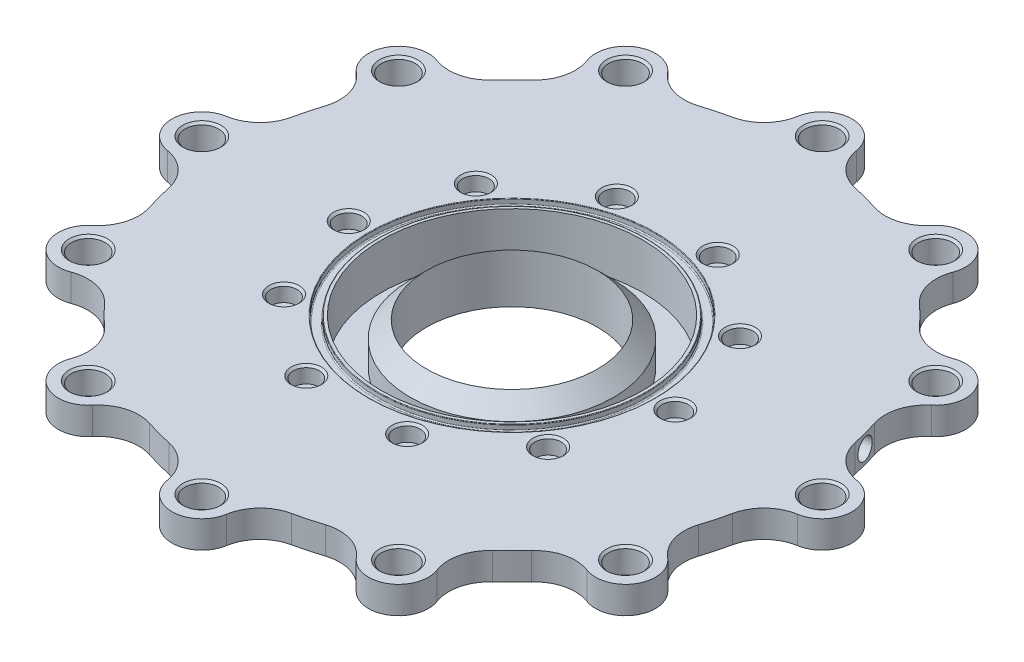
SolidWorks part; units mm, degrees
material "Inconel 718"
ref_plane "Front Plane" through (0, 0, 0) normal (0, 0, 1) x (1, 0, 0)
ref_plane "Top Plane" through (0, 0, 0) normal (0, 1, 0) x (1, 0, 0)
ref_plane "Right Plane" through (0, 0, 0) normal (1, 0, 0) x (0, 0, -1)
sketch "Sketch1" plane through (0, 0, 0) normal (0, 0, 1) x (1, 0, 0)
  line L0 (0, 0) -> (0, 36.0255) construction
  line L1 (50.198, 0) -> (42.578, 0)
  line L2 (19.939, 2.8778) -> (19.939, 14.3332) construction
  line L3 (30.48, 4.6203) -> (30.48, 15.24)
  line L4 (23.749, 4.6203) -> (30.48, 4.6203)
  line L5 (30.48, 15.24) -> (43.848, 15.24)
  line L6 (23.749, 14.3332) -> (23.749, 4.6203)
  line L7 (19.939, 14.3332) -> (23.749, 14.3332)
  line L8 (19.939, 2.8778) -> (31.148, 2.8778)
  line L9 (19.939, 2.8778) -> (19.939, 14.3332)
  line L10 (1037.8007, 0) -> (50.198, 0) construction
  line L12 (50.198, 10.6045) -> (50.198, 3.556)
  line L13 (30.48, 14.6164) -> (38.1, 14.6164) construction
  line L14 (0, 0) -> (-1001.6788, 0) construction
  line L15 (50.198, 1.524) -> (50.198, 0)
  line L16 (50.198, 1.524) -> (48.928, 1.524)
  line L18 (50.198, 3.556) -> (48.928, 3.556)
  line L19 (50.198, 10.6045) -> (59.723, 10.6045)
  line L20 (43.848, 15.24) -> (79.375, 15.24)
  line L21 (79.375, 15.24) -> (79.375, 8.89)
  line L22 (79.375, 8.89) -> (59.723, 8.89)
  line L23 (59.723, 8.89) -> (59.723, 10.6045)
  line L24 (48.928, 1.524) -> (48.928, 3.556)
  arc A0 (42.578, 0) -> (36.863, 1.4389) centre (42.578, 12.0687) cw
  arc A1 (36.863, 1.4389) -> (31.148, 2.8778) centre (31.148, -9.1909) ccw
  dimension "D9" = 79.375
  dimension "D10" = 11.43
  dimension "D12" = 19.652
  dimension "D2" = 19.939
  dimension "D3" = 30.48
  dimension "D4" = 23.749
  dimension "D5" = 15.24
  dimension "D6" = 14.3332
  dimension "D7" = 4.6203
  dimension "D8" = 2.8778
  dimension "D11" = 5.715
  dimension "D13" = 7.62
  dimension "D14" = 50.198
  dimension "D15" = 4.6355
  dimension "D16" = 8.89
  dimension "D17" = 1.27
  dimension "D18" = 2.032
  dimension "D19" = 1.524
revolve "Revolve1" add sketch "Sketch1" angle 360 about L0
chamfer "Chamfer2" distance 3.81 angle 45 1 edges at (0, 14.3332, -23.749)
hole_wizard "Hole3" positions "Sketch2" profile "Sketch3" legacy
sketch "Sketch2" plane through (0, 15.24, 0) normal (0, 1, 0) x (1, 0, 0)
  line L0 (38.1, 0) -> (0, 0) construction
  point P0 (38.1, 0)
  dimension "D1" = 38.1
sketch "Sketch3" plane through (38.1, 15.24, 0) normal (1, 0, 0) x (0, 0, 1)
  line L0 (0, 0) -> (0, 3.81)
  line L1 (0, 3.81) -> (3.048, 3.81)
  line L2 (3.048, 3.81) -> (3.048, 0)
  line L3 (3.048, 0) -> (0, 0)
  line L4 (0, 110) -> (0, -10) construction
  dimension "Diameter" = 6.096
  dimension "Depth" = 3.81
ref_plane "Plane1" through (38.1, 0, 0) normal (1, 0, 0) x (0, 0, -1)
sketch "Sketch4" plane through (38.1, 0, 0) normal (1, 0, 0) x (0, 0, -1)
  line L1 (0, 12.954) -> (-1.5705, 12.954)
  line L3 (-1.5705, 12.954) -> (-1.5705, 12.079)
  line L4 (0, 15.24) -> (0, 12.954) construction
  line L5 (-1.5705, 12.079) -> (-2, 11.6495)
  line L6 (-2, 11.6495) -> (-2, 6.3835)
  line L7 (-2, 6.3835) -> (-1.5705, 5.954)
  line L8 (-1.5705, 5.954) -> (0, 5.954)
  line L9 (0, -200000) -> (0, 200036.0255) construction
  line L10 (0, 5.954) -> (0, 12.954)
  dimension "D1" = 1.5705
  dimension "D2" = 0.875
  dimension "D3" = 135
  dimension "D4" = 5.266
  dimension "D5" = 1.5705
  dimension "D6" = 0.4295
  dimension "D7" = 2.286
hole_wizard "M4x0.7 Tapped Hole1" positions "Sketch5" profile "Sketch7" tap size "M4x0.7" standard "ANSI Metric"
sketch "Sketch5" plane through (0, 11.43, 0) normal (0, 1, 0) x (1, 0, 0)
  point P0 (38.1, 0)
sketch "Sketch7" plane through (38.1, 11.43, 0) normal (1, 0, 0) x (0, 0, 1)
  line L0 (0, 0) -> (0, 8.1034)
  line L1 (0, 8.1034) -> (1.65, 7.112)
  line L2 (1.65, 7.112) -> (1.65, 0)
  line L5 (1.65, 0) -> (0, 0)
  line L10 (0, 8.1034) -> (-1.65, 7.112) construction
  line L11 (0, -6.35) -> (0, 107.95) construction
  dimension "Tap Drill Dia." = 3.3
  dimension "Tap Drill Depth" = 7.112
  dimension "Drill Angle" = 118
cosmetic thread "Hole Thread5" parameters "D1"=0, "D2"=4.3
pattern_circular "CirPattern1" count 10 over 360 about axis through (0, 10.5232, 0) along (0, 1, 0) of "Hole3", "M4x0.7 Tapped Hole1"
sketch "Sketch8" plane through (0, 0, 0) normal (0, 0, 1) x (1, 0, 0)
  line L1 (38.9084, 15.24) -> (-38.9084, 15.24) construction
  line L2 (0, 15.24) -> (0, 0) construction
  line L3 (33.3883, 15.24) -> (31.2547, 15.24)
  line L4 (33.3883, 15.24) -> (33.3883, 13.9192)
  line L5 (33.3883, 13.9192) -> (31.2547, 13.9192)
  line L6 (31.2547, 15.24) -> (31.2547, 13.9192)
  dimension "D1" = 2.1336
  dimension "D2" = 1.3208
  dimension "D3" = 33.3883
revolve "Cut-Revolve1" cut sketch "Sketch8" angle 360 about L2
fillet "Fillet1" radius 0.127 2 edges at (0, 15.24, 31.2547) (0, 15.24, 33.3883)
fillet "Fillet2" radius 0.254 2 edges at (0, 13.9192, 33.3883) (0, 13.9192, 31.2547)
fillet "Fillet3" radius 0.127 2 edges at (0, 1.524, -50.198) (0, 3.556, -50.198)
hole_wizard "Hole4" positions "Sketch30" profile "Sketch31" legacy end condition through all
sketch "Sketch30" plane through (0, 15.24, 0) normal (0, 1, 0) x (1, 0, 0)
  line L0 (0, 72.39) -> (0, 0) construction
  point P0 (0, 72.39)
  dimension "D1" = 72.39
sketch "Sketch31" plane through (0, 15.24, -72.39) normal (1, 0, 0) x (0, 0, 1)
  line L0 (0, 0) -> (0, 15.24)
  line L1 (0, 15.24) -> (3.937, 15.24)
  line L2 (3.937, 15.24) -> (3.937, 0)
  line L3 (3.937, 0) -> (0, 0)
  line L4 (0, 110) -> (0, -10) construction
  dimension "Diameter" = 7.874
  dimension "Depth" = 15.24
pattern_circular "CirPattern2" count 12 over 360 about axis through (0, 14.3332, 0) along (0, -1, 0) of "Hole4"
sketch "Sketch33" plane through (0, 15.24, 0) normal (0, 1, 0) x (1, 0, 0)
  line L0 (0, 0) -> (79.375, 0) construction
  line L1 (0, 0) -> (68.7408, 39.6875) construction
  arc A0 (79.375, 0) -> (73.5318, 6.891) centre (72.39, 0) ccw
  arc A1 (79.375, 0) -> (68.7408, 39.6875) centre (0, 0) ccw
  arc A2 (67.1259, 30.7981) -> (68.7408, 39.6875) centre (62.6916, 36.195) ccw
  arc A3 (65.7802, 14.2688) -> (64.1017, 20.533) centre (0, 0) ccw
  arc A4 (65.7802, 14.2688) -> (73.5318, 6.891) centre (75.0887, 16.2879) ccw
  arc A5 (67.1259, 30.7981) -> (64.1017, 20.533) centre (73.1727, 23.4386) ccw
  circle A6 centre (72.39, 0) radius 3.937 construction
  circle A7 centre (62.6916, 36.195) radius 3.937 construction
  circle A8 centre (0, 0) radius 79.375 construction
  circle A9 centre (72.39, 0) radius 3.937
  circle A10 centre (62.6916, 36.195) radius 3.937
  dimension "D1" = 19.05
  dimension "D2" = 67.31
extrude "Cut-Extrude1" cut sketch "Sketch33" against normal through all
pattern_circular "CirPattern3" count 12 over 360 about axis through (0, 14.3332, 0) along (0, -1, 0) of "Cut-Extrude1"
sketch "Sketch34" plane through (0, 15.24, 0) normal (0, 1, 0) x (1, 0, 0)
  line L3 (0, 0) -> (65.0165, 17.4211)
  arc A2 (65.7802, 14.2688) -> (64.1017, 20.533) centre (0, 0) ccw construction
ref_plane "Plane2" through (65.0165, 15.24, -17.4211) normal (0.9659, 0, -0.2588) x (-0.2588, 0, -0.9659)
hole_wizard "Hole6" positions "3DSketch4" profile "Sketch39" legacy
sketch3d "3DSketch4"
  line L0 (65.0165, 15.24, -17.4211) -> (65.0165, 8.89, -17.4211) construction
  arc A0 (65.7802, 8.89, -14.2688) -> (64.1017, 8.89, -20.533) centre (0, 8.89, 0) ccw construction
  point P3 (65.0165, 12.065, -17.4211)
  point P22 (0, 76.2, 0)
  point P25 (65.0165, 12.065, -17.4211)
sketch "Sketch39" plane through (65.0165, 12.065, -17.4211) normal (0, 1, 0) x (-0.2588, 0, -0.9659)
  line L0 (0, 0) -> (0, 11.43)
  line L1 (0, 11.43) -> (0.7938, 11.43)
  line L2 (0.7938, 11.43) -> (0.7938, 6.35)
  line L3 (0.7938, 6.35) -> (2.3813, 6.35)
  line L4 (2.3813, 6.35) -> (2.3813, 0)
  line L5 (2.3813, 0) -> (0, 0)
  line L6 (0, 110) -> (0, -10) construction
  dimension "Diameter" = 1.5875
  dimension "Depth" = 11.43
  dimension "C-Bore Diameter" = 4.7625
  dimension "C-Bore Depth" = 6.35
ref_plane "Plane3" through (53.9759, 0, -14.4628) normal (0.9659, 0, -0.2588) x (-0.2588, 0, -0.9659)
sketch "Sketch50" plane through (53.9759, 0, -14.4628) normal (0.9659, 0, -0.2588) x (-0.2588, 0, -0.9659)
  line L0 (0, 12.8588) -> (0, 9.303)
  line L1 (0.7938, 12.065) -> (3.4181, 9.303)
  line L2 (3.4181, 9.303) -> (0, 9.303)
  circle A0 centre (0, 12.065) radius 0.7938 construction
  arc A1 (0.7938, 12.065) -> (0, 12.8588) centre (0, 12.065) ccw
  point P1 (0, 0)
  point P2 (0, 0)
  dimension "D3" = 0.7938
  dimension "D1" = 2.762
  dimension "D4" = 3.81
revolve "Cut-Revolve2" cut sketch "Sketch50" angle 360 about L0
chamfer "Chamfer3" distance 0.508 angle 45 10 edges at (30.8235, 15.24, 25.4426) (11.7735, 15.24, 39.2833) (-11.7735, 15.24, 39.2833) (-30.8235, 15.24, 25.4426) (-38.1, 15.24, 3.048) (-30.8235, 15.24, -19.3466) (-11.7735, 15.24, -33.1873) (11.7735, 15.24, -33.1873) (30.8235, 15.24, -19.3466) (38.1, 15.24, 3.048)
chamfer "Chamfer4" distance 0.508 angle 45 24 edges at (0, 15.24, -68.453) (0, 8.89, -76.327) (-36.195, 15.24, -58.7546) (-36.195, 8.89, -66.6286) (-62.6916, 15.24, -32.258) (-62.6916, 8.89, -40.132) (-72.39, 15.24, 3.937) (-72.39, 8.89, -3.937) (-62.6916, 15.24, 40.132) (-62.6916, 8.89, 32.258) (-36.195, 15.24, 66.6286) (-36.195, 8.89, 58.7546) (0, 15.24, 76.327) (0, 8.89, 68.453) (36.195, 15.24, 66.6286) (36.195, 8.89, 58.7546) (62.6916, 15.24, 40.132) (62.6916, 8.89, 32.258) (72.39, 15.24, 3.937) (72.39, 8.89, -3.937) (62.6916, 15.24, -32.258) (62.6916, 8.89, -40.132) (36.195, 15.24, -58.7546) (36.195, 8.89, -66.6286)
